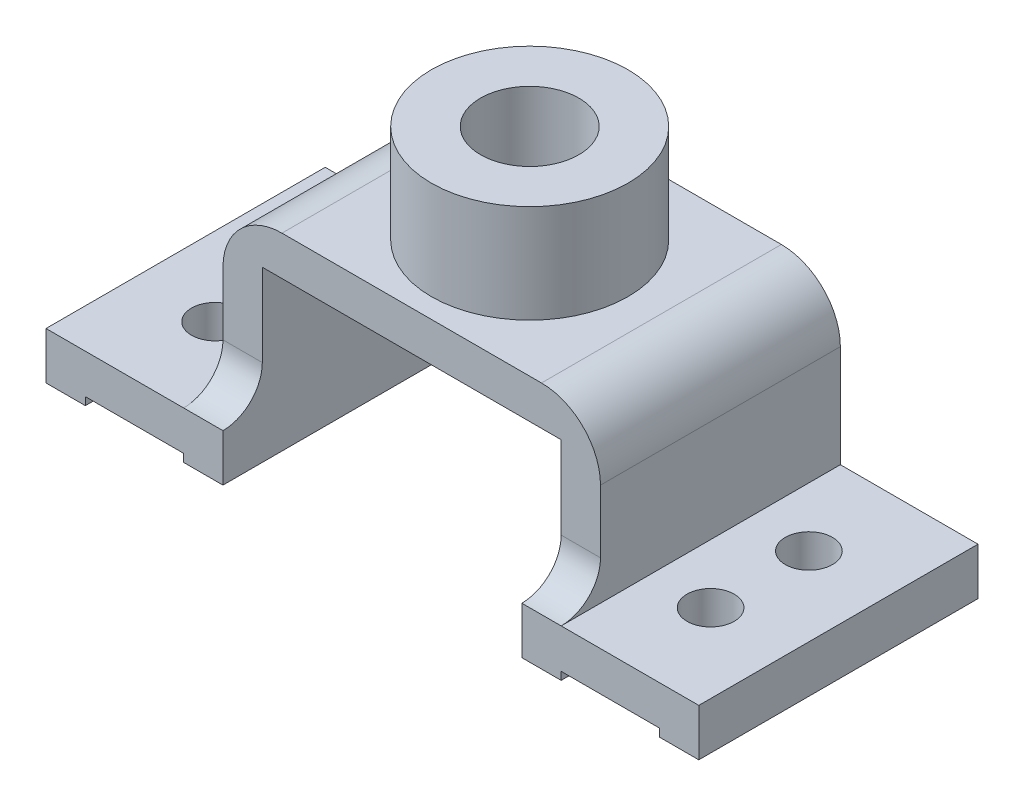
SolidWorks part; units mm, degrees
ref_plane "Front Plane" through (0, 0, 0) normal (0, 0, 1) x (1, 0, 0)
ref_plane "Top Plane" through (0, 0, 0) normal (0, 1, 0) x (1, 0, 0)
ref_plane "Right Plane" through (0, 0, 0) normal (1, 0, 0) x (0, 0, -1)
sketch "Sketch2" plane through (0, 0, 0) normal (0, 0, 1) x (1, 0, 0)
  line L0 (-43.0477, -3.5356) -> (-33.0477, -3.5356)
  line L1 (-33.0477, -3.5356) -> (-33.0477, -1.5356)
  line L2 (-33.0477, -1.5356) -> (-8.0477, -1.5356)
  line L3 (-8.0477, -1.5356) -> (-8.0477, -3.5356)
  line L4 (-8.0477, -3.5356) -> (1.9523, -3.5356)
  line L5 (1.9523, -3.5356) -> (1.9523, 8.4644)
  line L6 (1.9523, 8.4644) -> (-43.0477, 8.4644)
  line L7 (-43.0477, 8.4644) -> (-43.0477, -3.5356)
  line L8 (77.9523, -3.5356) -> (77.9523, 8.4644)
  line L9 (77.9523, 8.4644) -> (122.9523, 8.4644)
  line L10 (122.9523, 8.4644) -> (122.9523, -3.5356)
  line L11 (122.9523, -3.5356) -> (112.9523, -3.5356)
  line L12 (112.9523, -3.5356) -> (112.9523, -1.5356)
  line L13 (112.9523, -1.5356) -> (87.9523, -1.5356)
  line L14 (87.9523, -1.5356) -> (87.9523, -3.5356)
  line L15 (87.9523, -3.5356) -> (77.9523, -3.5356)
  dimension "D1" = 12
  dimension "D2" = 10
  dimension "D3" = 10
  dimension "D4" = 10
  dimension "D5" = 12
  dimension "D6" = 12
  dimension "D7" = 12
  dimension "D8" = 10
  dimension "D9" = 10
  dimension "D10" = 10
  dimension "D11" = 25
  dimension "D12" = 25
  dimension "D13" = 166
  dimension "D14" = 45
  dimension "D15" = 45
extrude "Boss-Extrude1" add sketch "Sketch2" against normal blind 71
ref_plane "Plane2" through (0, 0, -10) normal (0, 0, 1) x (1, 0, 0)
sketch "Sketch5" plane through (0, 0, -10) normal (0, 0, 1) x (1, 0, 0)
  line L0 (1.9523, 8.4644) -> (1.9523, 39.4644)
  line L1 (1.9523, 39.4644) -> (77.9523, 39.4644)
  line L2 (77.9523, 39.4644) -> (77.9523, 8.4644)
  line L3 (122.9523, 8.4644) -> (77.9523, 8.4644) construction
  line L4 (77.9523, 8.4644) -> (77.9523, -3.5356) construction
  line L5 (77.9523, 8.4644) -> (87.9523, 8.4644)
  line L6 (87.9523, 8.4644) -> (87.9523, 49.4644)
  line L7 (87.9523, 49.4644) -> (-8.0477, 49.4644)
  line L8 (-8.0477, 49.4644) -> (-8.0477, 8.4644)
  line L9 (1.9523, 8.4644) -> (-43.0477, 8.4644) construction
  line L10 (-8.0477, 8.4644) -> (1.9523, 8.4644)
  point P3 (77.9523, 38.0913)
  dimension "D1" = 10
  dimension "D2" = 10
  dimension "D3" = 10
  dimension "D4" = 43
extrude "Boss-Extrude3" add sketch "Sketch5" against normal blind 61
fillet "Fillet2" radius 10 2 edges at (82.9523, 8.4644, -10) (-3.0477, 8.4644, -10)
fillet "Fillet3" radius 15 2 edges at (87.9523, 49.4644, -40.5) (-8.0477, 49.4644, -40.5)
sketch "Sketch6" plane through (0, 49.4644, 0) normal (0, 1, 0) x (1, 0, 0)
  line L0 (72.9523, 10) -> (6.9523, 10) construction
  line L1 (6.9523, 71) -> (6.9523, 10) construction
  circle A0 centre (39.9523, 40) radius 25
  circle A1 centre (39.9523, 40) radius 12.5
  dimension "D1" = 50
  dimension "D2" = 25
  dimension "D3" = 30
  dimension "D4" = 33
extrude "Boss-Extrude4" add sketch "Sketch6" along normal blind 25
hole_wizard "Ø12.0mm Dowel Slot1" positions "Sketch7" profile "Sketch8" size "Ø12.0" standard "DIN" slot yes end condition through all
sketch "Sketch7" plane through (0, 8.4644, 0) normal (0, 1, 0) x (1, 0, 0)
  line L0 (122.9523, 71) -> (122.9523, 0) construction
  line L1 (122.9523, 71) -> (87.9523, 71) construction
  point P0 (102.9523, 48)
  point P2 (102.9523, 23)
  dimension "D1" = 20
  dimension "D2" = 25
  dimension "D3" = 20
  dimension "D4" = 23
sketch "Sketch8" plane through (102.9523, 8.4644, -48) normal (1, 0, 0) x (0, 0, 1)
  line L0 (0, 0) -> (0, 12)
  line L1 (0, 12) -> (6, 12)
  line L2 (6, 12) -> (6, 0)
  line L5 (6, 0) -> (0, 0)
  line L11 (0, -6.35) -> (0, 107.95) construction
  dimension "Thru Hole Dia." = 12
  dimension "Thru Hole Depth" = 12
hole_wizard "Ø12.0mm Dowel Slot2" positions "Sketch9" profile "Sketch10" size "Ø12.0" standard "DIN" slot yes end condition through all
sketch "Sketch9" plane through (0, 8.4644, 0) normal (0, 1, 0) x (1, 0, 0)
  line L0 (-43.0477, 71) -> (-43.0477, 0) construction
  line L1 (-8.0477, 71) -> (-43.0477, 71) construction
  point P0 (-23.0477, 23)
  point P2 (-23.0477, 48)
  point P9 (-25.5477, 71)
  dimension "D1" = 20
  dimension "D2" = 20
  dimension "D3" = 25
  dimension "D4" = 23
sketch "Sketch10" plane through (-23.0477, 8.4644, -23) normal (1, 0, 0) x (0, 0, 1)
  line L0 (0, 0) -> (0, 12)
  line L1 (0, 12) -> (6, 12)
  line L2 (6, 12) -> (6, 0)
  line L5 (6, 0) -> (0, 0)
  line L11 (0, -6.35) -> (0, 107.95) construction
  dimension "Thru Hole Dia." = 12
  dimension "Thru Hole Depth" = 12
